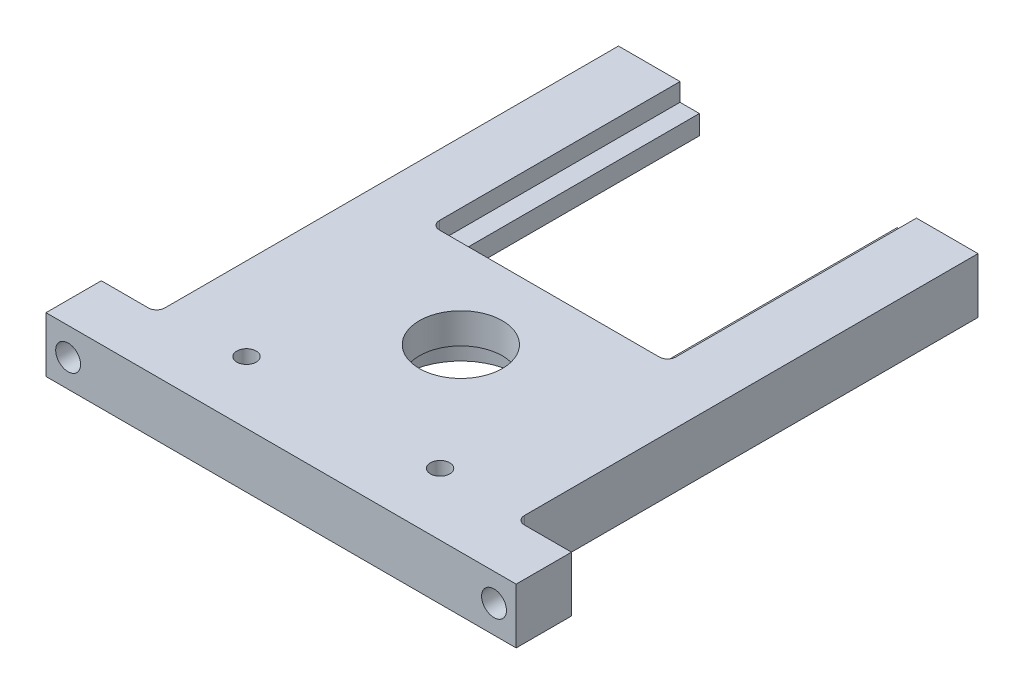
SolidWorks part; units mm, degrees
ref_plane "Front Plane" through (0, 0, 0) normal (0, 0, 1) x (1, 0, 0)
ref_plane "Top Plane" through (0, 0, 0) normal (0, 1, 0) x (1, 0, 0)
ref_plane "Right Plane" through (0, 0, 0) normal (1, 0, 0) x (0, 0, -1)
sketch "Sketch1" plane through (0, 0, 0) normal (0, 1, 0) x (1, 0, 0)
  line L0 (-85, 0) -> (85, 0)
  line L1 (85, 0) -> (85, 20)
  line L2 (85, 20) -> (68, 20)
  line L3 (65, 23) -> (65, 187)
  line L4 (65, 187) -> (42.75, 187)
  line L5 (42.75, 187) -> (42.75, 100)
  line L6 (32.75, 97) -> (-32.75, 97)
  line L8 (35.75, 187) -> (35.75, 100)
  line L9 (42.75, 187) -> (35.75, 187)
  line L10 (42.75, 187) -> (42.75, 97) construction
  line L11 (35.75, 187) -> (35.75, 97) construction
  line L12 (39.75, 97) -> (32.75, 97)
  line L13 (-35.75, 187) -> (-35.75, 100)
  line L14 (-39.75, 97) -> (-32.75, 97)
  line L15 (-42.75, 187) -> (-42.75, 100)
  line L16 (-65, 187) -> (-35.75, 187)
  line L17 (-65, 23) -> (-65, 187)
  line L18 (-85, 20) -> (-68, 20)
  line L19 (-85, 0) -> (-85, 20)
  arc A0 (42.75, 100) -> (39.75, 97) centre (39.75, 100) cw
  arc A2 (35.75, 100) -> (32.75, 97) centre (32.75, 100) cw
  circle A4 centre (0, 65) radius 15
  circle A7 centre (35, 22.5) radius 3.5
  arc A8 (65, 23) -> (68, 20) centre (68, 23) ccw
  arc A9 (-42.75, 100) -> (-39.75, 97) centre (-39.75, 100) ccw
  arc A10 (-65, 23) -> (-68, 20) centre (-68, 23) cw
  circle A11 centre (-35, 22.5) radius 3.5
  arc A12 (-35.75, 100) -> (-32.75, 97) centre (-32.75, 100) ccw
  dimension "D4" = 3
  dimension "D1" = 7
extrude "Boss-Extrude1" add sketch "Sketch1" along normal mid plane 20 contours L17 A10 L18 L19 L0 L1 L2 A8 L3 L4 L5 A0 L12 L6 L14 A9 L15 L16 A7 A4 A11 region at (-82.4728, 0, -10)
extrude "Boss-Extrude2" add sketch "Sketch1<4>" along normal mid plane 7 contours A12 L13 L16 L15 A9 L14 | L8 A2 L12 A0 L5 L9 region at (-39.2285, 0, -142) region at (39.2285, 0, -142)
sketch "Sketch1<4>" plane through (0, 0, 0) normal (0, 1, 0) x (1, 0, 0) same geometry as "Sketch1"
sketch "Sketch2" plane through (0, -10, 0) normal (0, -1, 0) x (1, 0, 0)
  circle A0 centre (0, -65) radius 21
extrude "Cut-Extrude1" cut sketch "Sketch2" against normal blind 9
hole_wizard "Ø1.0mm Dowel Hole1" positions "Sketch4" profile "Sketch5" hole size "Ø1.0" standard "ISO"
sketch "Sketch4" plane through (0, 0, -97) normal (0, 0, -1) x (-1, 0, 0)
  point P0 (-25, 0)
  point P4 (25, 0)
  dimension "D1" = 25
  dimension "D2" = 25
sketch "Sketch5" plane through (25, 0, -97) normal (1, 0, 0) x (0, 1, 0)
  line L0 (0, 0) -> (0, 5)
  line L1 (0, 5) -> (3.5, 5)
  line L2 (3.5, 5) -> (3.5, 0)
  line L5 (3.5, 0) -> (0, 0)
  line L10 (0, 5) -> (-3.5, 5) construction
  line L11 (0, -6.35) -> (0, 107.95) construction
  dimension "Hole Dia." = 7
  dimension "Hole Depth" = 5
  dimension "Drill Angle" = 180
sketch "Sketch6" plane through (0, 0, 0) normal (0, 0, 1) x (1, 0, 0)
  circle A2 centre (77, 0) radius 4.5
  circle A3 centre (-77, 0) radius 4.5
extrude "Cut-Extrude2" cut sketch "Sketch6" against normal blind 20
hole_wizard "M6 Tapped Hole1" positions "Sketch7" profile "Sketch8" tap size "M6" standard "ISO"
sketch "Sketch7" plane through (0, 0, -187) normal (0, 0, -1) x (-1, 0, 0)
  line L0 (65, 10) -> (65, -10) construction
  point P0 (55, 0)
  point P5 (65, 0)
  dimension "D1" = 10
sketch "Sketch8" plane through (-55, 0, -187) normal (1, 0, 0) x (0, 1, 0)
  line L0 (0, 0) -> (0, 15)
  line L1 (0, 15) -> (2.5, 15)
  line L2 (2.5, 15) -> (2.5, 0)
  line L5 (2.5, 0) -> (0, 0)
  line L10 (0, 15) -> (-2.5, 15) construction
  line L11 (0, -6.35) -> (0, 107.95) construction
  dimension "Tap Drill Dia." = 5
  dimension "Tap Drill Depth" = 15
  dimension "Drill Angle" = 180
cosmetic thread "Hole Thread1" parameters "D1"=15, "D2"=6
hole_wizard "M6 Tapped Hole2" positions "Sketch9" profile "Sketch10" tap size "M6" standard "ISO"
sketch "Sketch9" plane through (0, 0, -187) normal (0, 0, -1) x (-1, 0, 0)
  line L0 (-65, 10) -> (-65, -10) construction
  point P0 (-55, 0)
  dimension "D1" = 10
sketch "Sketch10" plane through (55, 0, -187) normal (1, 0, 0) x (0, 1, 0)
  line L0 (0, 0) -> (0, 15)
  line L1 (0, 15) -> (2.5, 15)
  line L2 (2.5, 15) -> (2.5, 0)
  line L5 (2.5, 0) -> (0, 0)
  line L10 (0, 15) -> (-2.5, 15) construction
  line L11 (0, -6.35) -> (0, 107.95) construction
  dimension "Tap Drill Dia." = 5
  dimension "Tap Drill Depth" = 15
  dimension "Drill Angle" = 180
cosmetic thread "Hole Thread2" parameters "D1"=15, "D2"=6
